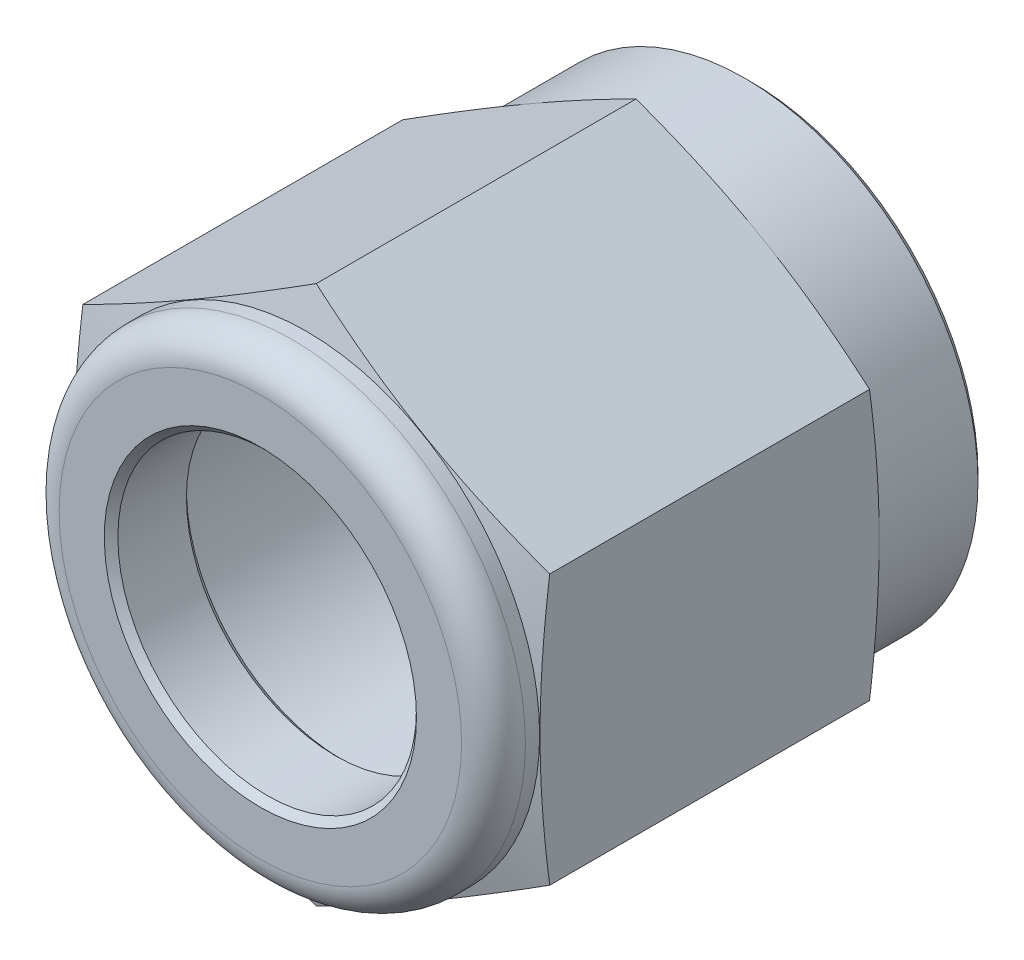
SolidWorks part; units mm, degrees
material "2024-T4"
ref_plane "Front Plane" through (0, 0, 0) normal (0, 0, 1) x (1, 0, 0)
ref_plane "Top Plane" through (0, 0, 0) normal (0, 1, 0) x (1, 0, 0)
ref_plane "Right Plane" through (0, 0, 0) normal (1, 0, 0) x (0, 0, -1)
sketch "Sketch0" plane through (0, 0, 0) normal (1, 0, 0) x (0, 0, -1)
  line L0 (0, 0) -> (-18.3896, 0) construction
  line L4 (-18.3896, 8.7376) -> (-18.3896, -8.7376) construction
  line L5 (-18.3896, 8.7249) -> (-18.3896, -8.7249) construction
  line L6 (-18.3896, 5.588) -> (-18.3896, -5.588) construction
  line L7 (0, 7.1438) -> (0, -7.1438) construction
  line L8 (0, -7.1374) -> (0, 7.1374) construction
  line L9 (0, -7.1374) -> (-1.4111, -7.1374) construction
  point P16 (-15.3162, 0)
  point P20 (-14.4526, 0)
  point P22 (-10.4902, 0)
  point P34 (-3.9624, 0)
  point P35 (-16.6624, 0)
  dimension "P" = 17.4752
  dimension "M" = 18.3896
  dimension "L" = 15.3162
  dimension "S" = 14.4526
  dimension "Q" = 10.4902
  dimension "A" = 11.176
  dimension "C" = 17.4498
  dimension "T" = 14.2875
  dimension "B" = 3.9624
  dimension "J" = 12.7
  dimension "H" = 14.2748
  dimension "Pitch" = 1.4111
sketch "Sketch1" plane through (0, 0, 0) normal (0, 0, 1) x (1, 0, 0)
  line L1 (0, 10.0893) -> (-8.7376, 5.0447)
  line L2 (-8.7376, 5.0447) -> (-8.7376, -5.0447)
  line L3 (-8.7376, -5.0447) -> (0, -10.0893)
  line L4 (0, -10.0893) -> (8.7376, -5.0447)
  line L5 (8.7376, -5.0447) -> (8.7376, 5.0447)
  line L6 (8.7376, 5.0447) -> (0, 10.0893)
  circle A0 centre (0, 0) radius 8.7376 construction
extrude "Boss-Extrude1" add sketch "Sketch1" along normal up to vertex (18.3896 mm away) up to point (0, 0, 18.3896)
sketch "Sketch2" plane through (0, 0, 0) normal (1, 0, 0) x (0, 0, -1)
  line L0 (-18.3896, 11.4537) -> (-18.3896, 8.7249)
  line L1 (-18.3896, 8.7249) -> (-16.6624, 8.7249)
  line L2 (-16.6624, 8.7249) -> (-16.2968, 10.0893)
  line L3 (-18.3896, 10.0893) -> (0, 10.0893) construction
  line L4 (-16.2968, 10.0893) -> (-4.328, 10.0893)
  line L5 (-4.328, 10.0893) -> (-3.9624, 8.7249)
  line L6 (-3.9624, 8.7249) -> (-16.6624, 8.7249) construction
  line L7 (-3.9624, 8.7249) -> (0, 8.7249)
  line L8 (0, 8.7249) -> (0, 11.4537)
  line L9 (-18.3896, 11.4537) -> (0, 11.4537)
  line L10 (-3.9624, 8.7249) -> (-3.9624, 0) construction
  line L11 (-16.6624, 8.7249) -> (-16.6624, 0) construction
  line L12 (-18.3896, 5.588) -> (-18.3896, 0)
  line L13 (-18.3896, 8.7376) -> (-18.3896, -8.7376) construction
  line L14 (-18.3896, 0) -> (0, 0)
  line L15 (0, 0) -> (0, 6.3704)
  line L16 (-15.3162, 5.588) -> (-15.3162, 0) construction
  line L17 (-15.3162, 5.588) -> (-15.3162, 6.1164)
  line L18 (-15.0622, 6.3704) -> (0, 6.3704)
  line L19 (-15.3162, 5.588) -> (-18.3896, 5.588)
  line L23 (-14.4526, 0) -> (-14.4526, 6.3704) construction
  arc A0 (-15.3162, 6.1164) -> (-15.0622, 6.3704) centre (-15.0622, 6.1164) cw
  dimension "D3" = 0.254
  dimension "D1" = 15
  dimension "D2" = 15
  dimension "D4" = 0.7733
revolve "Cut-Revolve1" cut sketch "Sketch2" angle 360 about L0
sketch "Sketch3" [suppressed] plane through (0, 0, 0) normal (0, 0, -1) x (-1, 0, 0)
  circle A0 centre (0, 0) radius 6.3704
  circle A1 centre (0, 0) radius 6.3704 construction
  point P3 (0, 6.3704)
fillet "Fillet1" radius 1.1938 1 edges at (0, 8.7249, 18.3896)
chamfer "Chamfer1" distance 0.254 angle 45 1 edges at (0, 8.7249, 0)
chamfer "Chamfer2" distance 0.254 angle 45 2 edges at (0, 5.588, 15.3162) (0, 5.588, 18.3896)
ref_axis "Centre Axis 1" through (0, 0, 25.2505) along (0, 0, -1)
curve "Helix/Spiral1" [suppressed] pitch 1.4111 height 15.8637 turns 11.242 parameters "Pitch"=1.4111
sketch "Sketch4" [suppressed] plane through (0, 0, 0) normal (1, 0, 0) x (0, 0, -1)
  line L0 (-0.248, 5.9408) -> (1.1631, 5.9408) construction
  line L1 (1.1631, 5.9408) -> (0.4575, 7.1628) construction
  line L2 (0.4575, 7.1628) -> (-0.248, 5.9408) construction
  line L3 (0.3583, 6.991) -> (0.5567, 6.991) construction
  line L4 (0.4575, 6.3704) -> (0.4575, 5.9408) construction
  line L5 (0, 6.3704) -> (0.915, 6.3704) construction
  line L6 (0.4575, 7.1628) -> (0.4575, 6.991) construction
  line L7 (0.3583, 6.991) -> (-0.124, 6.1556)
  line L8 (-0.124, 6.1556) -> (1.039, 6.1556)
  line L9 (1.039, 6.1556) -> (0.5567, 6.991)
  arc A0 (0.5567, 6.991) -> (0.3583, 6.991) centre (0.4575, 6.9337) ccw
  point P6 (0.4575, 6.1556)
  dimension "D1" = 1.4111
  dimension "D2" = 1.2221
  dimension "D4" = 0.4296
  dimension "D3" = 0.1719
  dimension "D5" = 0.6206
sweep "Cut-Sweep1" [suppressed] cut profiles "Sketch4" path "Helix/Spiral1"
sketch "Sketch5" [suppressed] plane through (0, 0, 0) normal (0, 0, -1) x (-1, 0, 0)
  circle A0 centre (0, 0) radius 7.1374
extrude "Cut-Extrude1" [suppressed] cut sketch "Sketch5" against normal through all draft 45
sketch "Sketch6" [suppressed] plane through (0, 0, 0) normal (1, 0, 0) x (0, 0, -1)
  line L0 (-15.3162, 7.1628) -> (-10.4902, 7.1628)
  line L1 (-10.4902, 7.1628) -> (-14.4526, 6.3704)
  line L2 (-14.4526, 6.3704) -> (-15.3162, 6.3704)
  line L3 (-15.3162, 6.3704) -> (-15.3162, 7.1628)
  line L4 (-10.4902, 0) -> (-10.4902, 7.1628) construction
  line L5 (-14.4526, 0) -> (-14.4526, 6.3704) construction
  line L7 (-15.3162, 6.3704) -> (-15.3162, 0) construction
  line L8 (-15.0622, 6.3704) -> (0, 6.3704) construction
  line L9 (-10.4902, 7.1628) -> (0.4575, 7.1628) construction
revolve "Revolve1" [suppressed] add sketch "Sketch6" angle 360 about L0
sketch "SketchX" [suppressed] plane through (0, 0, 0) normal (0, 0, -1) x (-1, 0, 0)
  line L0 (0, 0) -> (-3.5687, 6.1812) construction
  line L1 (0, 10.0893) -> (-8.7376, 5.0447) construction
  circle A0 centre (0, 0) radius 7.1374 construction
equation "\"D3@Helix/Spiral1\"= \"Pitch@Sketch0\" + \"S@Sketch0\""
equation "\"D1@Sketch4\"=\"Pitch@Sketch0\""
equation "\"Pitch@Helix/Spiral1\"=\"Pitch@Sketch0\""
